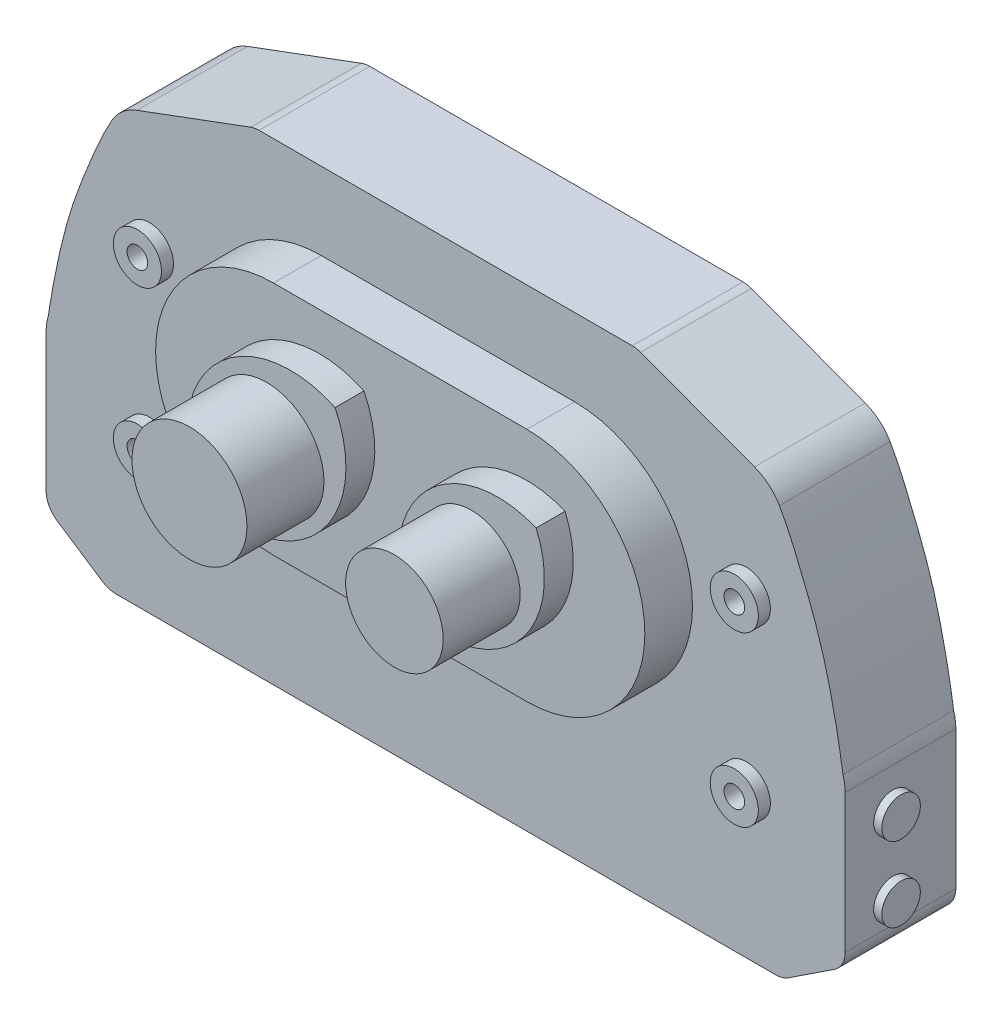
SolidWorks part; units mm, degrees
ref_plane "Front Plane" through (0, 0, 0) normal (0, 0, 1) x (1, 0, 0)
ref_plane "Top Plane" through (0, 0, 0) normal (0, 1, 0) x (1, 0, 0)
ref_plane "Right Plane" through (0, 0, 0) normal (1, 0, 0) x (0, 0, -1)
sketch "Sketch2" plane through (0, 0, 0) normal (0, 0, 1) x (1, 0, 0)
  line L0 (70.5234, -121.2586) -> (80.0018, -115.0085)
  line L1 (82.2493, -110.8343) -> (82.2493, -82.0607)
  line L2 (0, 0) -> (0, 97) construction
  line L3 (122.5391, 337.0673) -> (776.5391, 337.0673) construction
  line L4 (56.1264, 216.4843) -> (710.1264, 216.4843) construction
  line L5 (-39.52, -23.7969) -> (38.0186, -23.7969)
  line L6 (-0.7507, -122.0844) -> (-0.7507, -9.2148) construction
  line L7 (-83.7507, -110.8343) -> (-83.7507, -82.0607)
  line L8 (67.7709, -122.0844) -> (-69.2723, -122.0844)
  line L9 (-72.0248, -121.2586) -> (-81.5032, -115.0085)
  line L10 (-41.261, -24.1098) -> (-64.9089, -32.8935)
  line L11 (39.7596, -24.1098) -> (63.4075, -32.8935)
  line L14 (53.2993, -41.7763) -> (-54.8007, -41.7763) construction
  line L15 (-54.8007, -41.7763) -> (-54.8007, -107.2763) construction
  line L16 (-54.8007, -107.2763) -> (53.2993, -107.2763) construction
  line L17 (53.2993, -107.2763) -> (53.2993, -41.7763) construction
  arc A0 (-70.0862, -37.266) -> (-64.9089, -32.8935) centre (-61.427, -42.2677) cw
  arc A1 (-83.7507, -82.0607) -> (-83.2867, -79.0501) centre (-73.7507, -82.0607) cw
  arc A2 (-81.5032, -115.0085) -> (-83.7507, -110.8343) centre (-78.7507, -110.8343) cw
  arc A3 (-69.2723, -122.0844) -> (-72.0248, -121.2586) centre (-69.2723, -117.0844) cw
  arc A5 (67.7709, -122.0844) -> (70.5234, -121.2586) centre (67.7709, -117.0844) ccw
  arc A6 (80.0018, -115.0085) -> (82.2493, -110.8343) centre (77.2493, -110.8343) ccw
  arc A8 (82.2493, -82.0607) -> (81.7853, -79.0501) centre (72.2493, -82.0607) ccw
  arc A9 (-39.52, -23.7969) -> (-41.261, -24.1098) centre (-39.52, -28.7969) ccw
  arc A10 (68.5848, -37.266) -> (63.4075, -32.8935) centre (59.9256, -42.2677) ccw
  arc A11 (38.0186, -23.7969) -> (39.7596, -24.1098) centre (38.0186, -28.7969) cw
  spline S0 degree 3 poles (-83.2867, -79.0501) (-83.281, -79.0318) (-81.265, -64.2198) (-73.8122, -44.6321) (-71.5907, -39.8705) (-70.0862, -37.266) knots 0.010107 0.010107 0.010107 0.010107 0.430229 0.512694 0.834763 0.834763 0.834763 0.834763
  spline S1 degree 3 poles (81.7853, -79.0501) (81.7796, -79.0318) (79.7636, -64.2198) (72.3108, -44.6321) (70.0893, -39.8705) (68.5848, -37.266) knots 0.010107 0.010107 0.010107 0.010107 0.430229 0.512694 0.834763 0.834763 0.834763 0.834763
  point P5 (0, 0)
  point P13 (-0.7507, -23.7969)
  point P30 (38.9172, -23.7969)
  point P46 (-40.4186, -23.7969)
  point P49 (-0.7507, -41.7763)
  dimension "D1" = 10
  dimension "D2" = 10
  dimension "D3" = 5
  dimension "D4" = 5
  dimension "D5" = 166
  dimension "D6" = 5
extrude "Boss-Extrude1" add sketch "Sketch2" along normal blind 23
sketch "Sketch3" plane through (0, 0, 23) normal (0, 0, 1) x (1, 0, 0)
  line L0 (-0.7507, -23.7969) -> (-0.7507, -122.0844) construction
  line L1 (38.0186, -23.7969) -> (-39.52, -23.7969) construction
  line L2 (-69.2723, -122.0844) -> (67.7709, -122.0844) construction
ref_plane "Plane1" through (-0.7507, 0, 0) normal (-1, 0, 0) x (0, -1, 0)
sketch "Sketch5" plane through (-83.7507, 0, 0) normal (-1, 0, 0) x (0, 0, 1)
  line L0 (-44.9674, 914.2088) -> (400.4847, 914.2088) construction
  line L1 (13.0836, -123.8044) -> (13.0836, -90.5517) construction
  line L2 (-9.5774, -90.5517) -> (13.0836, -90.5517) construction
  line L3 (-9.5774, -106.0696) -> (13.0836, -106.0696) construction
  circle A0 centre (13.0836, -90.5517) radius 4
  circle A1 centre (13.0836, -106.0696) radius 4
extrude "Boss-Extrude3" add sketch "Sketch5" along normal blind 1.7
sketch "Sketch8" plane through (82.2493, 0, 0) normal (1, 0, 0) x (0, 0, -1)
  line L2 (0, -90.5507) -> (-13.08, -90.5507) construction
  line L4 (-13.08, -90.5507) -> (-13.08, -82.0607) construction
  line L6 (-13.08, -90.5507) -> (-13.08, -106.0707) construction
  circle A0 centre (-13.08, -90.5507) radius 4
  circle A1 centre (-13.08, -106.0707) radius 4
extrude "Boss-Extrude4" add sketch "Sketch8" along normal blind 1.7
sketch "Sketch12" plane through (0, 0, 23) normal (0, 0, 1) x (1, 0, 0)
  line L0 (20.3838, 54.9334) -> (416.3838, 54.9334) construction
  line L1 (26.0332, -39.8696) -> (-26.6057, -39.8696)
  line L2 (-26.6057, -39.8696) -> (-26.6057, -88.8696) construction
  line L3 (-26.6057, -88.8696) -> (26.0332, -88.8696)
  line L4 (-0.2862, -39.8696) -> (-0.2862, -88.8696) construction
  line L5 (-0.2862, -39.8696) -> (-0.2862, -24.7846) construction
  line L6 (-0.2862, -88.8696) -> (-0.2862, -121.7846) construction
  arc A0 (-26.6057, -39.8696) -> (-26.6057, -88.8696) centre (-26.6057, -64.3696) ccw
  arc A1 (26.0332, -39.8696) -> (26.0332, -88.8696) centre (26.0332, -64.3696) cw
  circle A2 centre (61.7138, -56.7846) radius 5
  circle A3 centre (61.7138, -91.7846) radius 5
  circle A4 centre (-62.2862, -91.7846) radius 5
  circle A5 centre (-62.2862, -56.7846) radius 5
  dimension "D1" = 62
  dimension "D3" = 62
  dimension "D5" = 10
  dimension "D6" = 10
  dimension "D9" = 10
  dimension "D10" = 10
  dimension "D11" = 97
  dimension "D2" = 62
  dimension "D4" = 62
  dimension "D7" = 35
  dimension "D8" = 35
  dimension "D12" = 30
  dimension "D13" = 30
  dimension "D14" = 49
extrude "Boss-Extrude5" add sketch "Sketch12" along normal blind 9.9
sketch "Sketch15" plane through (0, 0, 32.9) normal (0, 0, 1) x (1, 0, 0)
  line L0 (13.4386, 50.6195) -> (409.4386, 50.6195) construction
  line L1 (-7.8316, -49.9018) -> (-36.3069, -78.8976) construction
  line L2 (-0.2862, -39.8696) -> (-0.2862, -88.8696) construction
  line L3 (26.0332, -39.8696) -> (-26.6057, -39.8696) construction
  line L4 (-26.6057, -88.8696) -> (26.0332, -88.8696) construction
  line L5 (-22.0319, -64.3616) -> (20.4621, -64.3616) construction
  line L6 (7.057, -77.9762) -> (33.947, -50.666) construction
  circle A0 centre (-22.0319, -64.3616) radius 11.9456 construction
  arc A1 (-36.3069, -78.8976) -> (-7.8316, -49.9018) centre (-17.0867, -69.2928) cw
  arc A2 (-36.3069, -78.8976) -> (-7.8316, -49.9018) centre (-27.0518, -59.5066) ccw
  circle A3 centre (20.4621, -64.3616) radius 10.1338 construction
  arc A4 (33.947, -50.666) -> (7.057, -77.9762) centre (15.0085, -58.9121) cw
  arc A5 (33.947, -50.666) -> (7.057, -77.9762) centre (25.9955, -69.7301) ccw
extrude "Boss-Extrude6" add sketch "Sketch15" along normal blind 22
sketch "Sketch16" plane through (0, 0, 54.9) normal (0, 0, 1) x (1, 0, 0)
  line L0 (-7.8316, -49.9018) -> (-36.3069, -78.8976) construction
  circle A0 centre (-22.0693, -64.3997) radius 11.94
  arc A1 (-36.3069, -78.8976) -> (-7.8316, -49.9018) centre (-17.0867, -69.2928) cw
  arc A2 (-7.8316, -49.9018) -> (-36.3069, -78.8976) centre (-27.0518, -59.5066) cw
extrude "Cut-Extrude1" cut sketch "Sketch16" against normal blind 16
sketch "Sketch17" plane through (0, 0, 54.9) normal (0, 0, 1) x (1, 0, 0)
  line L0 (33.947, -50.666) -> (7.057, -77.9762) construction
  arc A0 (33.947, -50.666) -> (7.057, -77.9762) centre (25.9955, -69.7301) ccw construction
  arc A1 (7.057, -77.9762) -> (33.947, -50.666) centre (15.0085, -58.9121) ccw construction
  circle A2 centre (20.502, -64.3211) radius 10.13
  arc A3 (7.057, -77.9762) -> (33.947, -50.666) centre (25.9955, -69.7301) cw
  arc A4 (33.947, -50.666) -> (7.057, -77.9762) centre (15.0085, -58.9121) cw
extrude "Cut-Extrude2" cut sketch "Sketch17" against normal blind 16
sketch "Sketch18" plane through (0, 0, 32.9) normal (0, 0, 1) x (1, 0, 0)
  circle A0 centre (61.7138, -56.7846) radius 5.3096
extrude "Cut-Extrude3" cut sketch "Sketch18" against normal blind 7.4
sketch "Sketch19" plane through (0, 0, 32.9) normal (0, 0, 1) x (1, 0, 0)
  circle A0 centre (61.7138, -91.7846) radius 5.3836
extrude "Cut-Extrude4" cut sketch "Sketch19" against normal blind 7.4
sketch "Sketch20" plane through (0, 0, 32.9) normal (0, 0, 1) x (1, 0, 0)
  circle A0 centre (-62.2862, -56.7846) radius 5.4443
extrude "Cut-Extrude5" cut sketch "Sketch20" against normal blind 7.4
sketch "Sketch21" plane through (0, 0, 32.9) normal (0, 0, 1) x (1, 0, 0)
  circle A0 centre (-62.2862, -91.7846) radius 5.291
extrude "Cut-Extrude6" cut sketch "Sketch21" against normal blind 7.4
sketch "Sketch22" plane through (0, 0, 25.5) normal (0, 0, 1) x (1, 0, 0)
  circle A0 centre (-62.2862, -56.7846) radius 2.15
  circle A1 centre (-62.2862, -91.7846) radius 2.15
  circle A2 centre (61.7138, -91.7846) radius 2.15
  circle A3 centre (61.7138, -56.7846) radius 2.15
  dimension "D1" = 4.3
  dimension "D2" = 4.3
  dimension "D3" = 4.3
  dimension "D4" = 4.3
extrude "Cut-Extrude7" cut sketch "Sketch22" against normal blind 10
